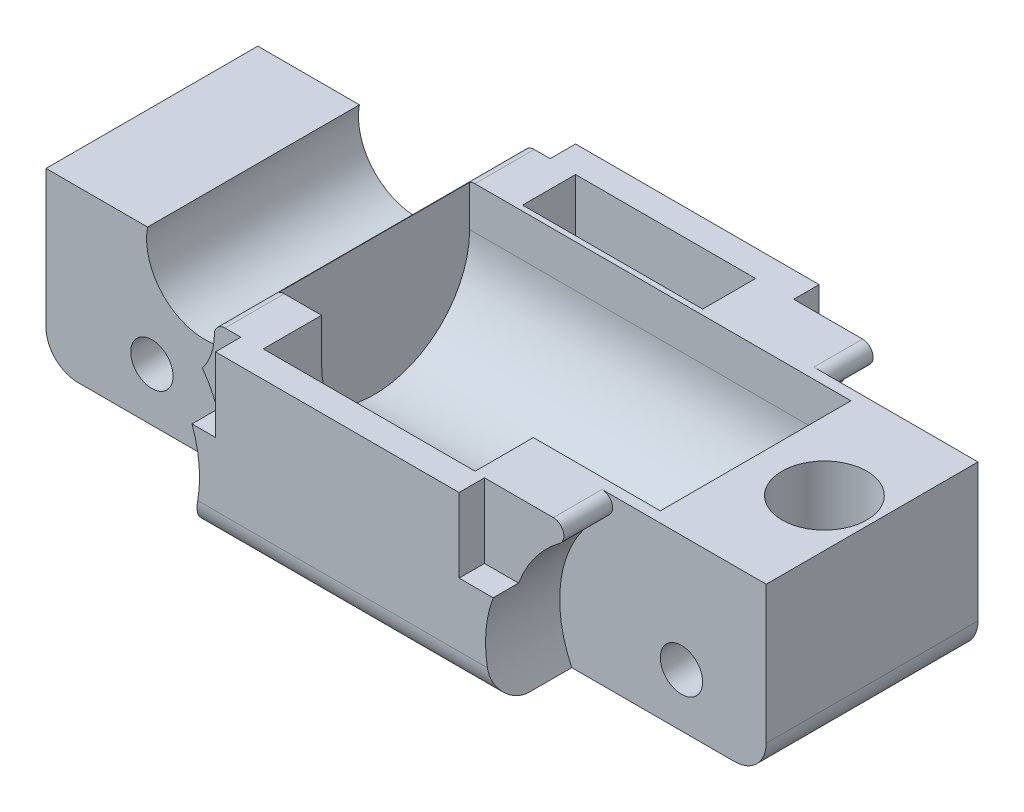
SolidWorks part; units mm, degrees
material "ABS"
ref_plane "Front Plane" through (0, 0, 0) normal (0, 0, 1) x (1, 0, 0)
ref_plane "Top Plane" through (0, 0, 0) normal (0, 1, 0) x (1, 0, 0)
ref_plane "Right Plane" through (0, 0, 0) normal (1, 0, 0) x (0, 0, -1)
sketch "Sketch1" plane through (0, 0, 0) normal (0, 1, 0) x (1, 0, 0)
  line L1 (-34, 17) -> (34, 17)
  line L2 (-34, 17) -> (-34, -17)
  line L3 (-34, -17) -> (34, -17)
  line L4 (34, 17) -> (34, -17)
  line L5 (-34, 17) -> (34, -17) construction
  line L6 (-34, -17) -> (34, 17) construction
  point P0 (0, 0)
  dimension "D1" = 68
  dimension "D2" = 34
extrude "Boss-Extrude1" add sketch "Sketch1" along normal blind 16
sketch "Sketch2" plane through (0, 0, 0) normal (0, 0, 1) x (1, 0, 0)
  point P0 (-24, 5)
  point P1 (26, 5)
  dimension "D1" = 50
  dimension "D2" = 26
  dimension "D3" = 5
sketch "Sketch3" plane through (0, 0, 0) normal (0, 0, 1) x (1, 0, 0)
  line L0 (26, 16.5) -> (37.5, 16.5)
  line L1 (37.5, 16.5) -> (37.5, 5)
  line L2 (37.5, 5) -> (37.5, -6.5)
  line L3 (37.5, -6.5) -> (26, -6.5)
  line L4 (-24, -6.5) -> (-35.5, -6.5)
  line L5 (-35.5, -6.5) -> (-35.5, 16.5)
  line L6 (-35.5, 16.5) -> (-24, 16.5)
  circle A0 centre (-24, 5) radius 11.5
  circle A1 centre (26, 5) radius 11.5
  dimension "D1" = 23
extrude "Cut-Extrude2" cut sketch "Sketch3" along normal blind 10 from offset 10 contours A1 L3 L2 | A1 | A1 L1 L0 | A0 | A0 L5 L4 | A0 L6 L5 region at (34.9313, 13.9313, 0) region at (26, 5, 0) region at (34.9313, -3.9313, 0) region at (-24, 5, 0) region at (-32.9313, -3.9313, 0) region at (-32.9313, 13.9313, 0)
mirror "Mirror1" about plane through (0, 0, 0) normal (0, 0, 1) of "Cut-Extrude2"
sketch "Sketch5" plane through (0, 0, 0) normal (0, 0, 1) x (1, 0, 0)
  circle A0 centre (26, 5) radius 2
  circle A1 centre (-24, 5) radius 2
  dimension "D1" = 4
extrude "Cut-Extrude3" cut sketch "Sketch5" against normal through all both and the other way through all
sketch "Sketch4" plane through (0, 0, 0) normal (1, 0, 0) x (0, 0, -1)
  line L0 (-9, 12) -> (-9, 23.0528)
  line L1 (-9, 23.0528) -> (9, 23.0528)
  line L2 (9, 23.0528) -> (9, 12)
  circle A0 centre (0, 12) radius 9
  dimension "D1" = 18
  dimension "D2" = 12
extrude "Battery" add sketch "Sketch4" along normal blind 23 and the other way blind 13 separate body contours A0 | A0 L2 L1 L0 region at (0, 17.5264, 8.7888) region at (0, 12, 0)
combine bodies "Combine1" operation type subtract main body 106 bodies to subtract 104
sketch "Sketch13" plane through (0, 16, 0) normal (0, 1, 0) x (1, 0, 0)
  circle A0 centre (29.5, 0) radius 4
  dimension "D1" = 8
  dimension "D2" = 29.5
extrude "MountHole" cut sketch "Sketch13" against normal blind 6
sketch "Sketch6" plane through (0, 0, 0) normal (0, 1, 0) x (1, 0, 0)
  line L1 (8.5, 9.5) -> (-8.5, 9.5)
  line L2 (8.5, 9.5) -> (8.5, 14.5)
  line L3 (8.5, 14.5) -> (-8.5, 14.5)
  line L4 (-8.5, 9.5) -> (-8.5, 14.5)
  line L5 (8.5, 9.5) -> (-8.5, 14.5) construction
  line L6 (8.5, 14.5) -> (-8.5, 9.5) construction
  point P0 (0, 12)
  dimension "D1" = 17
  dimension "D2" = 5
  dimension "D3" = 12
extrude "Charger" cut sketch "Sketch6" along normal up to next from offset 3
sketch "Sketch7" plane through (0, 0, 0) normal (0, -1, 0) x (1, 0, 0)
  line L1 (6, -16) -> (-6, -16)
  line L2 (6, -16) -> (6, -8)
  line L3 (6, -8) -> (-6, -8)
  line L4 (-6, -16) -> (-6, -8)
  line L5 (6, -16) -> (-6, -8) construction
  line L6 (6, -8) -> (-6, -16) construction
  point P0 (0, -12)
  dimension "D1" = 12
  dimension "D2" = 8
extrude "MicroUSB" cut sketch "Sketch7" against normal blind 3
fillet "Fillet1" radius 1.5 2 edges at (0, 3, -16) (0, 3, -8)
sketch "Sketch8" plane through (0, 0, 0) normal (0, 0, 1) x (1, 0, 0)
  circle A0 centre (-19, 15) radius 5.5
  dimension "D1" = 11
  dimension "D2" = 19
  dimension "D3" = 15
extrude "Motor" cut sketch "Sketch8" against normal through all both and the other way through all
sketch "Sketch9" plane through (0, 0, 0) normal (0, 0, 1) x (1, 0, 0)
  circle A0 centre (-19, 15) radius 4
fillet "BottomFillet_3mm" radius 3 4 edges at (1, 0, 17) (1, 0, -17) (34, 0, 0) (-34, 0, 0)
fillet "Fillet_1mm" radius 1 3 edges at (22.6459, 16, 13.5) (22.6459, 16, -13.5) (-13.5917, 16, 0)
sketch "Sketch10" plane through (0, 16, 0) normal (0, 1, 0) x (1, 0, 0)
  line L0 (-12.5, -17) -> (18.5, -17) construction
  line L1 (-8.983, -8.5) -> (11.017, -8.5)
  line L2 (-8.983, -8.5) -> (-8.983, -14.5)
  line L3 (-8.983, -14.5) -> (11.017, -14.5)
  line L4 (11.017, -8.5) -> (11.017, -14.5)
  line L5 (-8.983, -8.5) -> (11.017, -14.5) construction
  line L6 (-8.983, -14.5) -> (11.017, -8.5) construction
  point P0 (1.017, -11.5)
  dimension "D1" = 20
  dimension "D2" = 6
  dimension "D3" = 2.5
extrude "ControlBoard" cut sketch "Sketch10" against normal blind 12
fillet "Fillet2" radius 2 1 edges at (1.017, 9.042, 8.5)
hole_wizard "CSK for M3 Flat Head Machine Screw1" positions "Sketch11" profile "Sketch12" countersink size "M3" standard "ANSI Metric"
sketch "Sketch11" plane through (0, 0, 0) normal (0, -1, 0) x (-1, 0, 0)
  point P0 (-29.5, 0)
sketch "Sketch12" plane through (29.5, 0, 0) normal (1, 0, 0) x (0, 0, -1)
  line L0 (0, 0) -> (0, 11.0815)
  line L1 (0, 11.0815) -> (1.8, 10)
  line L2 (1.8, 10) -> (1.8, 1.35)
  line L3 (1.8, 1.35) -> (3.15, 0)
  line L5 (3.15, 0) -> (0, 0)
  line L6 (-1.8, 1.35) -> (-3.15, 0) construction
  line L10 (0, 11.0815) -> (-1.8, 10) construction
  line L11 (0, -6.35) -> (0, 107.95) construction
  dimension "Hole Dia." = 3.6
  dimension "Hole Depth" = 10
  dimension "Near C'Sink Dia." = 6.3
  dimension "Near C'Sink Angle" = 90
  dimension "Drill Angle" = 118
sketch "Sketch14" plane through (0, 0, 0) normal (0, 0, 1) x (1, 0, 0)
  line L1 (25.8393, 9) -> (12, 9)
  line L2 (25.8393, 9) -> (25.8393, 23.5989)
  line L3 (25.8393, 23.5989) -> (12, 23.5989)
  line L4 (12, 9) -> (12, 23.5989)
  line L5 (-22.7748, 9) -> (-11, 9)
  line L6 (-22.7748, 9) -> (-22.7748, 22.7145)
  line L7 (-22.7748, 22.7145) -> (-11, 22.7145)
  line L8 (-11, 9) -> (-11, 22.7145)
  dimension "D1" = 12
  dimension "D2" = 11
  dimension "D3" = 9
extrude "Cut-Extrude5" cut sketch "Sketch14" along normal blind 2.4 from vertex starting at point (18.5, 16, -17)
extrude "Cut-Extrude6" cut sketch "Sketch14<2>" against normal blind 2.4 from vertex starting at point (18.5, 16, 17)
sketch "Sketch14<2>" plane through (0, 0, 0) normal (0, 0, 1) x (1, 0, 0) same geometry as "Sketch14"
